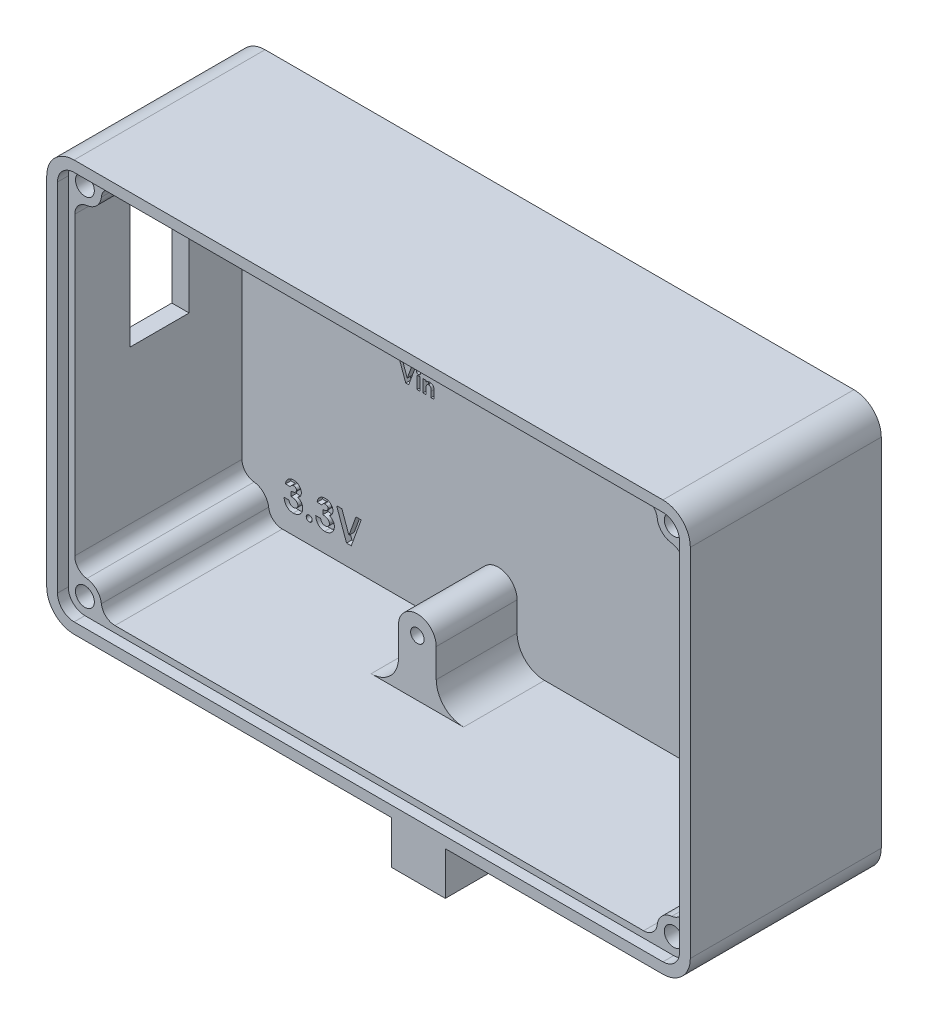
SolidWorks part; units mm, degrees
material "ABS"
ref_plane "Front Plane" through (0, 0, 0) normal (0, 0, 1) x (1, 0, 0)
ref_plane "Top Plane" through (0, 0, 0) normal (0, 1, 0) x (1, 0, 0)
ref_plane "Right Plane" through (0, 0, 0) normal (1, 0, 0) x (0, 0, -1)
sketch "OdroidOutline" plane through (0, 0, 0) normal (0, 0, 1) x (1, 0, 0)
  line L1 (42.5, -28) -> (-42.5, -28)
  line L2 (42.5, -28) -> (42.5, 28)
  line L3 (42.5, 28) -> (-42.5, 28)
  line L4 (-42.5, -28) -> (-42.5, 28)
  line L5 (42.5, -28) -> (-42.5, 28) construction
  line L6 (42.5, 28) -> (-42.5, -28) construction
  line L7 (-19, 24.5) -> (39, 24.5) construction
  line L8 (-19, 24.5) -> (-19, -24.5) construction
  line L9 (-19, -24.5) -> (39, -24.5) construction
  line L10 (39, 24.5) -> (39, -24.5) construction
  line L11 (-44, 25.54) -> (-22.3, 25.54)
  line L12 (-44, 25.54) -> (-44, 9.96)
  line L13 (-44, 9.96) -> (-22.3, 9.96)
  line L14 (-22.3, 25.54) -> (-22.3, 9.96)
  line L15 (-44, 5.565) -> (-26.44, 5.565)
  line L16 (-44, 5.565) -> (-44, -7.565)
  line L17 (-44, -7.565) -> (-26.44, -7.565)
  line L18 (-26.44, 5.565) -> (-26.44, -7.565)
  line L19 (-44, -12.435) -> (-26.44, -12.435)
  line L20 (-44, -12.435) -> (-44, -25.565)
  line L21 (-44, -25.565) -> (-26.44, -25.565)
  line L22 (-26.44, -12.435) -> (-26.44, -25.565)
  circle A0 centre (-19, 24.5) radius 1.25
  circle A1 centre (39, 24.5) radius 1.25
  circle A2 centre (39, -24.5) radius 1.25
  circle A3 centre (-19, -24.5) radius 1.25
  point P0 (0, 0)
  point P26 (-44, 17.75)
  point P27 (-44, -1)
  point P28 (-44, -19)
  dimension "D7" = 2.5
  dimension "D1" = 85
  dimension "D2" = 56
  dimension "D3" = 58
  dimension "D4" = 49
  dimension "D5" = 3.5
  dimension "D6" = 3.5
  dimension "D8" = 10.25
  dimension "D9" = 29
  dimension "D10" = 47
  dimension "D11" = 15.58
  dimension "D12" = 21.7
  dimension "D13" = 13.13
  dimension "D14" = 17.56
  dimension "D15" = 1.5
sketch "BatteryOutline" plane through (0, 0, 0) normal (0, 0, 1) x (1, 0, 0)
  line L0 (-4.2158, -21.195) -> (-4.2158, 21.195) construction
  line L2 (42.5, 0) -> (-4.2158, 0) construction
  line L3 (42.5, -28) -> (42.5, 28) construction
  line L4 (-4.2158, 21.195) -> (-4.2158, 24.5) construction
  line L7 (33.5342, -30.5) -> (-41.9658, -30.5)
  line L8 (33.5342, -30.5) -> (33.5342, 30.5)
  line L9 (33.5342, 30.5) -> (-41.9658, 30.5)
  line L10 (-41.9658, -30.5) -> (-41.9658, 30.5)
  line L11 (33.5342, -30.5) -> (-41.9658, 30.5) construction
  line L12 (33.5342, 30.5) -> (-41.9658, -30.5) construction
  circle A0 centre (-4.2158, 21.195) radius 1.75
  circle A1 centre (-4.2158, -21.195) radius 1.75
  point P3 (-4.2158, 0)
  dimension "D2" = 3.5
  dimension "D1" = 42.39
  dimension "D3" = 75.5
  dimension "D4" = 61
sketch "Sketch4" plane through (0, 0, 0) normal (0, 0, 1) x (1, 0, 0)
  line L0 (53.5, 0) -> (-53.5, 0) construction
  line L1 (53.5, -15) -> (53.5, 15) construction
  line L2 (-53.5, -15) -> (-53.5, 15) construction
  circle A0 centre (53.5, 15) radius 1.75
  circle A1 centre (-53.5, 15) radius 1.75
  circle A2 centre (-53.5, -15) radius 1.75
  circle A3 centre (53.5, -15) radius 1.75
  point P5 (0, 0)
  point P6 (53.5, 0)
  point P9 (-53.5, 0)
  dimension "D1" = 3.5
  dimension "D2" = 30
  dimension "D3" = 107
sketch "Sketch5" plane through (0, 0, 0) normal (0, 0, 1) x (1, 0, 0)
  line L0 (44.5696, 34.9) -> (-64.6504, 34.9)
  line L1 (44.5696, -38.1) -> (-64.6504, -38.1)
  line L2 (49.6496, -33.02) -> (49.6496, 33.02)
  line L3 (44.5696, 38.1) -> (-64.6504, 38.1)
  line L4 (-69.7304, -33.02) -> (-69.7304, 33.02)
  line L5 (49.6496, -38.1) -> (-69.7304, 38.1) construction
  line L6 (49.6496, 38.1) -> (-69.7304, -38.1) construction
  line L7 (-66.5304, -33.02) -> (-66.5304, 33.02)
  line L8 (44.5696, -34.9) -> (-64.6504, -34.9)
  line L9 (46.4496, -33.02) -> (46.4496, 33.02)
  arc A0 (-64.6504, -38.1) -> (-69.7304, -33.02) centre (-64.6504, -33.02) cw
  arc A1 (44.5696, -38.1) -> (49.6496, -33.02) centre (44.5696, -33.02) ccw
  arc A2 (49.6496, 33.02) -> (44.5696, 38.1) centre (44.5696, 33.02) ccw
  arc A3 (-64.6504, 38.1) -> (-69.7304, 33.02) centre (-64.6504, 33.02) ccw
  arc A4 (-64.6504, 34.9) -> (-66.5304, 33.02) centre (-64.6504, 33.02) ccw
  arc A5 (-64.6504, -34.9) -> (-66.5304, -33.02) centre (-64.6504, -33.02) cw
  arc A6 (44.5696, -34.9) -> (46.4496, -33.02) centre (44.5696, -33.02) ccw
  arc A7 (46.4496, 33.02) -> (44.5696, 34.9) centre (44.5696, 33.02) ccw
  dimension "D6" = 5.08
  dimension "D1" = 76.2
  dimension "D2" = 119.38
  dimension "D3" = 3.2
extrude "Enclosure Base" add sketch "Sketch5" along normal blind 2.4 contours L3 A3 L4 A0 L1 A1 L2 A2
extrude "Enclosure Wall" add sketch "Sketch5<3>" along normal blind 33.02 from surface contours L3 A3 L4 A0 L1 A1 L2 A2 A7 L9 A6 L8 A5 L7 A4 L0 region at (-10.0404, -36.6837, 0) starting at face at (-10.0404, 0, 2.4)
sketch "Sketch5<3>" plane through (0, 0, 0) normal (0, 0, 1) x (1, 0, 0) same geometry as "Sketch5"
sketch "Sketch6" plane through (0, 0, 2.4) normal (0, 0, 1) x (1, 0, 0)
  line L0 (42.5, 28) -> (-42.5, 28) construction
  line L1 (-22.5, 24.5) -> (-22.5, 34.9)
  line L2 (44.5696, 34.9) -> (-64.6504, 34.9) construction
  line L3 (-22.5, 34.9) -> (-15.5, 34.9)
  line L4 (-15.5, 34.9) -> (-15.5, 24.5)
  line L5 (10, 24.5) -> (10, 29.9225) construction
  line L6 (-19, 24.5) -> (39, 24.5) construction
  line L7 (39, 0) -> (30.934, 0) construction
  line L8 (39, 24.5) -> (39, -24.5) construction
  line L9 (35.5, 24.5) -> (35.5, 34.9)
  line L10 (35.5, 34.9) -> (42.5, 34.9)
  line L11 (42.5, 34.9) -> (42.5, 24.5)
  line L12 (-22.5, -24.5) -> (-22.5, -34.9)
  line L13 (44.5696, -34.9) -> (-64.6504, -34.9) construction
  line L14 (-22.5, -34.9) -> (-15.5, -34.9)
  line L15 (-15.5, -34.9) -> (-15.5, -24.5)
  line L16 (35.5, -24.5) -> (35.5, -34.9)
  line L17 (35.5, -34.9) -> (42.5, -34.9)
  line L18 (42.5, -34.9) -> (42.5, -24.5)
  arc A0 (-22.5, 24.5) -> (-15.5, 24.5) centre (-19, 24.5) ccw
  arc A1 (-15.5, -24.5) -> (-22.5, -24.5) centre (-19, -24.5) ccw
  arc A2 (35.5, 24.5) -> (42.5, 24.5) centre (39, 24.5) ccw
  arc A3 (42.5, -24.5) -> (35.5, -24.5) centre (39, -24.5) ccw
  circle A4 centre (39, -24.5) radius 1.25 construction
  circle A5 centre (39, 24.5) radius 1.25 construction
  circle A6 centre (-19, -24.5) radius 1.25 construction
  circle A7 centre (-19, 24.5) radius 1.25 construction
  circle A8 centre (39, -24.5) radius 1.25
  circle A9 centre (39, 24.5) radius 1.25
  circle A10 centre (-19, -24.5) radius 1.25
  circle A11 centre (-19, 24.5) radius 1.25
  arc A12 (-15.5, 24.5) -> (-22.5, 24.5) centre (-19, 24.5) ccw construction
  arc A13 (42.5, 24.5) -> (35.5, 24.5) centre (39, 24.5) ccw construction
  arc A14 (35.5, -24.5) -> (42.5, -24.5) centre (39, -24.5) ccw construction
  arc A15 (-22.5, -24.5) -> (-15.5, -24.5) centre (-19, -24.5) ccw construction
extrude "Odroid Mount Spacer" add sketch "Sketch6" along normal blind 15
sketch "Sketch7" plane through (-69.7304, 0, 0) normal (-1, 0, 0) x (0, 0, 1)
  line L1 (23.21, 0.9747) -> (12.21, 0.9747)
  line L2 (23.21, 0.9747) -> (23.21, 26.9747)
  line L3 (23.21, 26.9747) -> (12.21, 26.9747)
  line L4 (12.21, 0.9747) -> (12.21, 26.9747)
  line L5 (23.21, 0.9747) -> (12.21, 26.9747) construction
  line L6 (23.21, 26.9747) -> (12.21, 0.9747) construction
  line L7 (17.71, 33.02) -> (17.71, 13.9747) construction
  line L8 (35.42, 33.02) -> (0, 33.02) construction
  point P0 (17.71, 13.9747)
  dimension "D1" = 26
  dimension "D2" = 11
extrude "Power Switch Hole" cut sketch "Sketch7" against normal blind 7.112
sketch "Sketch8" plane through (0, 0, 2.4) normal (0, 0, 1) x (1, 0, 0)
  line L0 (-58.9104, 25.9564) -> (-58.9104, -31.1936) construction
  line L1 (-66.5304, -33.02) -> (-66.5304, 33.02) construction
  line L4 (49.6496, 38.1) -> (-69.7304, -38.1) construction
  text T0 "<b>3.3V</b>" font "Century Gothic" height 5.08
  text T1 "<b>5.0V</b>" font "Century Gothic" height 5.08
  text T2 "<b>Vin</b>" font "Century Gothic" height 3.175
  dimension "D1" = 57.15
  dimension "D2" = 7.62
extrude "Labeling" cut sketch "Sketch8" against normal blind 1
sketch "Sketch9" plane through (0, 0, 35.42) normal (0, 0, 1) x (1, 0, 0)
  line L0 (44.5696, 34.9) -> (-64.6504, 34.9) construction
  line L1 (46.4496, -33.02) -> (46.4496, 33.02) construction
  line L2 (44.5696, -34.9) -> (-64.6504, -34.9) construction
  line L3 (-66.5304, -33.02) -> (-66.5304, 33.02) construction
  line L4 (46.4496, -33.02) -> (46.4496, 33.02)
  line L5 (44.5696, -34.9) -> (-64.6504, -34.9)
  line L6 (-66.5304, -33.02) -> (-66.5304, 33.02)
  line L7 (44.5696, 34.9) -> (-64.6504, 34.9)
  line L8 (44.5696, 36.1) -> (-64.6504, 36.1)
  line L9 (-67.7304, 33.02) -> (-67.7304, -33.02)
  line L10 (-64.6504, -36.1) -> (44.5696, -36.1)
  line L11 (47.6496, -33.02) -> (47.6496, 33.02)
  line L12 (44.5696, 36.1) -> (-64.6504, 36.1)
  line L13 (-67.7304, 33.02) -> (-67.7304, -33.02)
  line L14 (-64.6504, -36.1) -> (44.5696, -36.1)
  line L15 (47.6496, -33.02) -> (47.6496, 33.02)
  arc A0 (46.4496, 33.02) -> (44.5696, 34.9) centre (44.5696, 33.02) ccw construction
  arc A1 (44.5696, -34.9) -> (46.4496, -33.02) centre (44.5696, -33.02) ccw construction
  arc A2 (-66.5304, -33.02) -> (-64.6504, -34.9) centre (-64.6504, -33.02) ccw construction
  arc A3 (-64.6504, 34.9) -> (-66.5304, 33.02) centre (-64.6504, 33.02) ccw construction
  arc A4 (46.4496, 33.02) -> (44.5696, 34.9) centre (44.5696, 33.02) ccw
  arc A5 (44.5696, -34.9) -> (46.4496, -33.02) centre (44.5696, -33.02) ccw
  arc A6 (-66.5304, -33.02) -> (-64.6504, -34.9) centre (-64.6504, -33.02) ccw
  arc A7 (-64.6504, 34.9) -> (-66.5304, 33.02) centre (-64.6504, 33.02) ccw
  arc A8 (47.6496, 33.02) -> (44.5696, 36.1) centre (44.5696, 33.02) ccw
  arc A9 (-64.6504, 36.1) -> (-67.7304, 33.02) centre (-64.6504, 33.02) ccw
  arc A10 (-67.7304, -33.02) -> (-64.6504, -36.1) centre (-64.6504, -33.02) ccw
  arc A11 (44.5696, -36.1) -> (47.6496, -33.02) centre (44.5696, -33.02) ccw
  arc A12 (47.6496, 33.02) -> (44.5696, 36.1) centre (44.5696, 33.02) ccw
  arc A13 (-64.6504, 36.1) -> (-67.7304, 33.02) centre (-64.6504, 33.02) ccw
  arc A14 (-67.7304, -33.02) -> (-64.6504, -36.1) centre (-64.6504, -33.02) ccw
  arc A15 (44.5696, -36.1) -> (47.6496, -33.02) centre (44.5696, -33.02) ccw
extrude "Top Cover Groove" cut sketch "Sketch9" against normal blind 2
sketch "Sketch10" plane through (0, 0, 0) normal (0, 0, 1) x (1, 0, 0)
  circle A0 centre (-64.6504, 33.02) radius 3.08
  circle A1 centre (-64.6504, -33.02) radius 3.08
  circle A2 centre (44.5696, 33.02) radius 3.08
  circle A3 centre (44.5696, -33.02) radius 3.08
  arc A4 (47.6496, 33.02) -> (44.5696, 36.1) centre (44.5696, 33.02) ccw construction
  arc A5 (-64.6504, 36.1) -> (-67.7304, 33.02) centre (-64.6504, 33.02) ccw construction
  arc A6 (-67.7304, -33.02) -> (-64.6504, -36.1) centre (-64.6504, -33.02) ccw construction
  arc A7 (44.5696, -36.1) -> (47.6496, -33.02) centre (44.5696, -33.02) ccw construction
  circle A8 centre (-64.6504, 33.02) radius 1.75
  circle A9 centre (-64.6504, -33.02) radius 1.75
  circle A10 centre (44.5696, -33.02) radius 1.75
  circle A11 centre (44.5696, 33.02) radius 1.75
  dimension "D1" = 3.5
extrude "Boss-Extrude4" add sketch "Sketch10" along normal up to surface (33.42 mm away) up to face at (-10.0404, 0, 33.42)
fillet "Fillet1" radius 2.54 8 edges at (46.4496, 30.5803, 17.91) (42.1299, 34.9, 25.41) (-62.2107, 34.9, 17.91) (-66.5304, 30.5803, 17.91) (-66.5304, -30.5803, 17.91) (-62.2107, -34.9, 17.91) (42.1299, -34.9, 25.41) (46.4496, -30.5803, 17.91)
sketch "Sketch11" plane through (0, 0, 2.4) normal (0, 0, 1) x (1, 0, 0)
  line L1 (21.3865, 7.3925) -> (-1.1635, 7.3925)
  line L2 (21.3865, 7.3925) -> (21.3865, 24.6925)
  line L3 (21.3865, 24.6925) -> (-1.1635, 24.6925)
  line L4 (-1.1635, 7.3925) -> (-1.1635, 24.6925)
  line L5 (21.3865, 7.3925) -> (-1.1635, 24.6925) construction
  line L6 (21.3865, 24.6925) -> (-1.1635, 7.3925) construction
  point P0 (10.1115, 16.0425)
  dimension "D1" = 17.3
  dimension "D2" = 22.55
ref_plane "Plane2" through (0, 0, 34.4) normal (0, 0, 1) x (1, 0, 0)
sketch "Sketch12" plane through (0, 0, 0) normal (0, 0, -1) x (-1, 0, 0)
  line L0 (5.7994, -38.1) -> (5.7994, -46.1)
  line L1 (-44.5696, -38.1) -> (64.6504, -38.1) construction
  line L2 (5.7994, -46.1) -> (-4.2006, -46.1)
  line L3 (-4.2006, -46.1) -> (-4.2006, -38.1)
  line L4 (5.7994, -38.1) -> (-4.2006, -38.1)
  dimension "D1" = 8
  dimension "D2" = 10
extrude "Boss-Extrude5" add sketch "Sketch12" against normal up to surface (35.42 mm away) up to face at (-10.0404, 0, 35.42)
sketch "Sketch15" plane through (0, 0, 2.4) normal (0, 0, 1) x (1, 0, 0)
  line L1 (-100.2631, 17.9297) -> (-79.2631, 17.9297) construction
  line L2 (-100.2631, 17.9297) -> (-100.2631, -24.0703) construction
  line L3 (-100.2631, -24.0703) -> (-79.2631, -24.0703) construction
  line L4 (-79.2631, 17.9297) -> (-79.2631, -24.0703) construction
  dimension "D1" = 21
  dimension "D2" = 42
sketch "Sketch16" plane through (0, -46.1, 0) normal (0, -1, 0) x (1, 0, 0)
  line L0 (-0.7994, 30.42) -> (-0.7994, 5.2274) construction
  line L1 (4.2006, 35.42) -> (-5.7994, 35.42) construction
  line L2 (-0.7994, 30.42) -> (-0.7994, 35.42) construction
  circle A0 centre (-0.7994, 30.42) radius 1.75
  circle A1 centre (-0.7994, 5.2274) radius 1.75
  dimension "D1" = 3.5
  dimension "D2" = 5
extrude "Cut-Extrude1" cut sketch "Sketch16" against normal up to surface (8 mm away) up to face at (24.3851, -38.1, 17.71)
fillet "Fillet2" radius 5.08 8 edges at (42.5, -30.739, 9.9) (35.5, -34.9, 9.9) (-15.5, -34.9, 9.9) (-22.5, -34.9, 9.9) (-15.5, 34.9, 9.9) (35.5, 34.9, 9.9) (42.5, 30.739, 9.9) (-22.5, 34.9, 9.9)
equation "\"D1@OdroidOutline\"=85mm"
equation "\"D2@OdroidOutline\"=56mm"
equation "\"D3@OdroidOutline\"=58mm"
equation "\"D4@OdroidOutline\"=49mm"
equation "\"D5@OdroidOutline\"=3.5mm"
equation "\"D6@OdroidOutline\"=3.5mm"
equation "\"D7@OdroidOutline\"=2.5mm"
equation "\"D9@OdroidOutline\"=29mm"
equation "\"D10@OdroidOutline\"=47mm"
equation "\"D11@OdroidOutline\"=15.58mm"
equation "\"D13@OdroidOutline\"=13.13mm"
equation "\"D15@OdroidOutline\"=1.5mm"
equation "\"D1@BatteryOutline\" = 42.39mm"
equation "\"D2@BatteryOutline\" = 3.5mm"
equation "\"D1@Sketch4\"=3.5mm"
equation "\"D2@Sketch4\"=30mm"
equation "\"D3@Sketch4\"=107mm"
equation "\"D3@Sketch5\"=3.2mm"
equation "\"D1@Enclosure Base\" = 2.4mm"
equation "\"D1@Enclosure Wall\" = 1.3in"
equation "\"D1@Odroid Mount Spacer\"=15mm"
equation "\"D4@BatteryOutline\" = 61mm"
equation "\"D1@Sketch7\"=26mm"
equation "\"D2@Sketch7\"=11mm"
equation "\"D1@Labeling\" = 1mm"
equation "\"D1@Sketch9\"=2mm"
equation "\"D1@Top Cover Groove\" = 2mm"
equation "\"D1@Sketch10\"=3.50mm"
equation "\"D1@Sketch11\"=17.3mm"
equation "\"D2@Sketch11\"=22.55mm"
equation "\"D1\" = 3.6mm"
equation "\"D1\" = 20mm"
equation "\"D1@Sketch12\"=8mm"
equation "\"D2@Sketch12\"=10mm"
equation "\"D1@Sketch15\"=21mm"
equation "\"D2@Sketch15\"=42mm"
equation "\"D1@Sketch16\"=3.5mm"
equation "\"D2@Sketch16\"=5mm"
equation "\"D1\" = 8mm"
